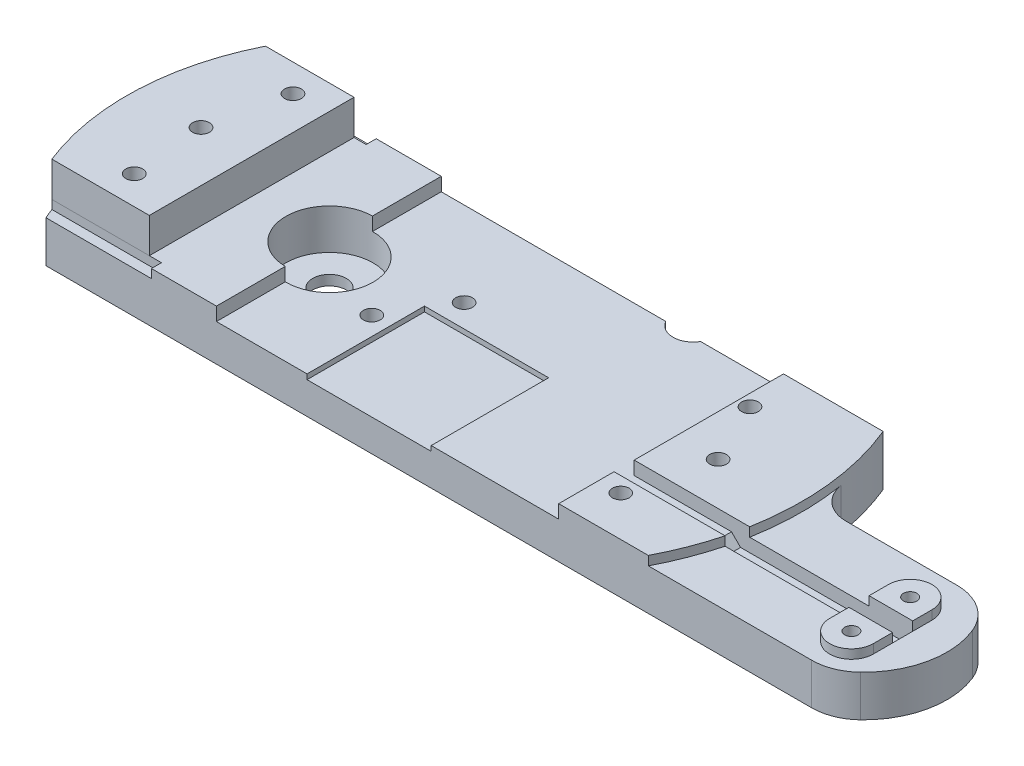
SolidWorks part; units mm, degrees
ref_plane "Front Plane" through (0, 0, 0) normal (0, 0, 1) x (1, 0, 0)
ref_plane "Top Plane" through (0, 0, 0) normal (0, 1, 0) x (1, 0, 0)
ref_plane "Right Plane" through (0, 0, 0) normal (1, 0, 0) x (0, 0, -1)
sketch "Sketch1" plane through (0, 0, 0) normal (0, 1, 0) x (1, 0, 0)
  line L1 (-97.5, -33.5) -> (97.5, -33.5)
  line L2 (-97.5, -33.5) -> (-97.5, 33.5)
  line L3 (-97.5, 33.5) -> (97.5, 33.5)
  line L4 (97.5, -33.5) -> (97.5, 33.5)
  line L5 (-97.5, -33.5) -> (97.5, 33.5) construction
  line L6 (-97.5, 33.5) -> (97.5, -33.5) construction
  point P0 (0, 0)
  dimension "D1" = 67
  dimension "D2" = 195
extrude "Boss-Extrude1" add sketch "Sketch1" along normal blind 25.4
sketch "Sketch2" plane through (0, 0, 0) normal (0, -1, 0) x (1, 0, 0)
  line L0 (-97.5, -33.5) -> (-97.5, 33.5) construction
  line L1 (97.5, 33.5) -> (97.5, -33.5) construction
  line L2 (97.5, 33.5) -> (88.5, 33.5)
  line L3 (-97.5, 33.5) -> (97.5, 33.5) construction
  line L4 (97.5, -33.5) -> (91.5, -33.5)
  line L5 (97.5, -33.5) -> (-97.5, -33.5) construction
  line L6 (-97.5, 33.5) -> (-91, 33.5)
  line L7 (-97.5, -33.5) -> (-88, -33.5)
  circle A0 centre (18.0922, -3.2198) radius 79.4078
  circle A1 centre (-22.6589, 2.9929) radius 74.8411
  line M7 (97.5, -33.5) -> (97.5, 33.5)
  line M8 (97.5, 33.5) -> (-97.5, 33.5)
  line M9 (-97.5, 33.5) -> (-97.5, -33.5)
  line M10 (-97.5, -33.5) -> (97.5, -33.5)
  dimension "D1" = 9
  dimension "D2" = 6
  dimension "D3" = 6.5
  dimension "D4" = 9.5
extrude "Cut-Extrude1" cut sketch "Sketch2" against normal through all contours A0 M7 M8 | A0 M10 M7 | A1 M9 M10 | A1 M8 M9 region at (94.8284, 0, 24.4273) region at (95.7123, 0, -25.9883) region at (-95.5654, 0, 25.941) region at (-94.6839, 0, -24.4966)
sketch "Sketch3" plane through (0, 0, 33.5) normal (0, 0, -1) x (-1, 0, 0)
  line L0 (97.5, 25.4) -> (63.2, 25.4)
  line L2 (63.2, 25.4) -> (63.2, 15)
  line L3 (63.2, 15) -> (40.2, 15)
  line L4 (40.2, 15) -> (40.2, 11)
  line L5 (40.2, 11) -> (-61.8, 11)
  line L6 (-91.5, 25.4) -> (88, 25.4) construction
  line L10 (97.5, 0) -> (97.5, 25.4) construction
  line L11 (-61.8, 11) -> (-61.8, 15)
  line L12 (-61.8, 15) -> (-97.5, 15)
  line L13 (-97.5, 25.4) -> (-97.5, 0) construction
  line L14 (-97.5, 15) -> (-97.5, 25.4)
  line L15 (-97.5, 25.4) -> (63.2, 25.4)
  line M13 (-88.5, 0) -> (-88.5, 25.4)
  line M14 (-88.5, 25.4) -> (91, 25.4)
  dimension "D1" = 10.4
  dimension "D2" = 34.3
  dimension "D3" = 23
  dimension "D4" = 4
  dimension "D5" = 102
extrude "Cut-Extrude2" cut sketch "Sketch3" along normal through all contours L11 L12 L2 L3 L4 L5 M13 M14 | L2 L3 L4 L5 L11 L12 L14 L15 region at (12.2699, 18.7206, 33.5)
sketch "Sketch4" plane through (0, 25.4, 0) normal (0, 1, 0) x (1, 0, 0)
  line L0 (-59.5873, 33.5) -> (-59.5873, 30.5)
  line L1 (-63.2, 33.5) -> (-88, 33.5) construction
  line L2 (-59.5873, 30.5) -> (-89.5873, 30.5)
  line L3 (-59.5873, -33.5) -> (-59.5873, -30.5)
  line L4 (-91, -33.5) -> (-63.2, -33.5) construction
  line L5 (-59.5873, -30.5) -> (-92.2617, -30.5)
  line L6 (-59.5873, 33.5) -> (-63.2, 33.5)
  line L7 (-59.5873, -33.5) -> (-63.2, -33.5)
  arc A0 (-88, 33.5) -> (-91, -33.5) centre (-22.6589, -2.9929) ccw construction
  line M5 (-91, -33.5) -> (-63.2, -33.5)
  line M6 (-63.2, -33.5) -> (-63.2, 33.5)
  line M7 (-63.2, 33.5) -> (-88, 33.5)
  arc M8 (-88, 33.5) -> (-91, -33.5) centre (-22.6589, -2.9929) ccw
  dimension "D1" = 3
  dimension "D2" = 3
  dimension "D3" = 30
extrude "Cut-Extrude3" cut sketch "Sketch4" against normal blind 13 contours L2 M6 M7 M8 | L0 L6 L2 M6 | L5 M6 M8 M5 | L7 L3 L5 M6 region at (-61.3937, 25.4, -32) region at (-76.0082, 25.4, -31.9845) region at (-77.4242, 25.4, 31.9889) region at (-61.3937, 25.4, 32)
sketch "Sketch6" plane through (0, 0, 0) normal (0, -1, 0) x (1, 0, 0)
  line L0 (-63.2, -33.5) -> (-97.5, -33.5)
  line L1 (91.5, -33.5) -> (-88, -33.5) construction
  line L2 (-63.2, -33.5) -> (-63.2, 33.5)
  line L3 (-91, 33.5) -> (88.5, 33.5) construction
  line L4 (-63.2, -9) -> (-28.1, -9) construction
  line L5 (-63.2, 8.7) -> (-18.7, 8.7) construction
  line L6 (-63.2, -8.3) -> (-8.2, -8.3) construction
  line L8 (91.5, -33.5) -> (-88, -33.5) construction
  line L9 (-97.5, -33.5) -> (-97.5, 33.5)
  line L10 (-97.5, 33.5) -> (-63.2, 33.5)
  circle A1 centre (-18.7, 8.7) radius 2.5
  circle A2 centre (74.1, -1.7) radius 2.5
  circle A3 centre (68.3, 21.5) radius 2.5
  circle A4 centre (65.3, -20) radius 2.5
  circle A5 centre (-8.2, -8.3) radius 2.5
  circle A6 centre (-76.2, 22) radius 2.5
  circle A7 centre (-78.2, 0.1) radius 2.5
  circle A8 centre (-73.2, -22.3) radius 2.5
  arc A10 (-91, 33.5) -> (-88, -33.5) centre (-22.6589, 2.9929) ccw construction
  dimension "D22" = 5
  dimension "D3" = 35.1
  dimension "D4" = 34.3
  dimension "D5" = 44.5
  dimension "D6" = 24.5
  dimension "D7" = 55
  dimension "D8" = 42.2
  dimension "D9" = 137.3
  dimension "D10" = 128.5
  dimension "D11" = 131.5
  dimension "D12" = 10
  dimension "D13" = 15
  dimension "D14" = 13
  dimension "D15" = 11.2
  dimension "D16" = 33.6
  dimension "D17" = 55.5
  dimension "D18" = 31.8
  dimension "D19" = 55
  dimension "D20" = 13.5
  dimension "D21" = 25.2
extrude "Cut-Extrude4" cut sketch "Sketch6" against normal through all contours A5 | A1 | A6 | A7 | A8 | A4 | A2 | A3 region at (-18.7, 0, 8.7) region at (74.1, 0, -1.7) region at (68.3, 0, 21.5) region at (65.3, 0, -20) region at (-8.2, 0, -8.3) region at (-76.2, 0, 22) region at (-78.2, 0, 0.1) region at (-73.2, 0, -22.3)
sketch "Sketch7" plane through (0, 11, 0) normal (0, 1, 0) x (1, 0, 0)
  line L1 (-13.2, 1.5) -> (23.8, 1.5)
  line L2 (-13.2, 1.5) -> (-13.2, -33.5)
  line L3 (-13.2, -33.5) -> (23.8, -33.5)
  line L4 (23.8, 1.5) -> (23.8, -33.5)
  line L8 (-63.2, 30.5) -> (-63.2, -30.5) construction
  line L9 (-63.2, 30.5) -> (-63.2, -30.5) construction
  line L10 (-40.2, -33.5) -> (61.8, -33.5) construction
  dimension "D1" = 50
  dimension "D2" = 87
  dimension "D3" = 35
extrude "Cut-Extrude5" cut sketch "Sketch7" against normal blind 1.5
sketch "Sketch8" plane through (0, 25.4, 0) normal (0, 1, 0) x (1, 0, 0)
  line L0 (-59.5873, -33.5) -> (-97.5, -33.5)
  line L1 (-97.5, -33.5) -> (-97.5, 33.5)
  line L3 (-97.5, 33.5) -> (31.9, 33.5)
  line L6 (31.9, 36.5) -> (31.9, 30.5)
  line L7 (31.9, 33.5) -> (37.0962, 33.5)
  line L10 (-59.5873, 33.5) -> (-88, 33.5) construction
  line L11 (-40.2, 33.5) -> (61.8, 33.5) construction
  circle A1 centre (31.9, 36.5) radius 6
  arc A2 (-89.5873, 30.5) -> (-92.2617, -30.5) centre (-22.6589, -2.9929) ccw construction
  dimension "D1" = 12
  dimension "D2" = 129.4
extrude "Cut-Extrude6" cut sketch "Sketch8" against normal blind 18.5 contours L6 A1 L7 | L3 A1 L6 region at (29.8648, 25.4, -32.2699) region at (33.9352, 25.4, -32.2699)
sketch "Sketch9" plane through (0, 0, 0) normal (0, -1, 0) x (1, 0, 0)
  line L0 (88.5, 33.5) -> (137.2004, 33.5)
  line L1 (139.5727, -7.5) -> (97.3846, -7.5)
  arc A0 (153.4738, 1.8643) -> (147.5429, 29.3643) centre (130.3054, 11.2571) ccw
  arc A1 (91.5, -33.5) -> (88.5, 33.5) centre (18.0922, -3.2198) ccw construction
  arc A2 (142.3827, -10.6321) -> (147.5429, 29.3643) centre (130.3054, 11.2571) ccw construction
  arc A3 (147.5429, 29.3643) -> (137.2004, 33.5) centre (137.2004, 18.5) ccw
  arc A4 (147.5429, 29.3643) -> (137.9704, 33.4802) centre (137.2004, 18.5) ccw construction
  arc A5 (139.5727, -7.5) -> (153.4738, 1.8643) centre (139.5727, 7.5) ccw
  circle A6 centre (112.8948, -27.5) radius 16 construction
  circle A7 centre (103.4238, 59.4942) radius 16 construction
  circle A8 centre (112.8948, -27.5) radius 20 construction
  arc A9 (97.3846, -7.5) -> (88.5, 33.5) centre (18.0922, -3.2198) ccw
  circle A10 centre (138.3, 5.25) radius 2
  circle A11 centre (138.3, 22.75) radius 2
  circle A12 centre (138.3, 22.75) radius 2 construction
  circle A13 centre (138.3, 5.25) radius 2 construction
  point P35 (112.8948, -27.5)
  dimension "D1" = 4
extrude "Boss-Extrude2" add sketch "Sketch9" against normal offset from surface (12.3 mm away) 1.3 up to face at (-16.2, 11, 8.7) offset beyond the face yes
fillet "Fillet1" radius 10 1 edges at (97.3846, 6.15, -7.5)
sketch "Sketch10" plane through (0, 0, 0) normal (0, -1, 0) x (1, 0, 0)
  circle A0 centre (-40.0178, 0) radius 13
  dimension "D1" = 26
extrude "Cut-Extrude7" cut sketch "Sketch10" against normal up to surface (15 mm away) from offset 3 up to face at (-55.6437, 15, 0) offset against normal yes
sketch "Sketch13" plane through (0, 0, 0) normal (0, -1, 0) x (1, 0, 0)
  circle A0 centre (-40.0178, 0) radius 5
  dimension "D1" = 10
extrude "Cut-Extrude9" cut sketch "Sketch13" against normal through all
sketch "Sketch11" plane through (0, 12.3, 0) normal (0, 1, 0) x (1, 0, 0)
  line L0 (138.3, -5.25) -> (138.3, -22.75) construction
  line L1 (144.8, -5.25) -> (144.8, -22.75)
  line L2 (131.8, -5.25) -> (131.8, -22.75)
  line L3 (131.8, -11) -> (144.8, -11)
  line L4 (131.8, -17) -> (144.8, -17)
  line L5 (131.8, -14) -> (144.8, -14) construction
  arc A0 (144.8, -5.25) -> (131.8, -5.25) centre (138.3, -5.25) ccw
  arc A1 (131.8, -22.75) -> (144.8, -22.75) centre (138.3, -22.75) ccw
  point P4 (138.3, -14)
  circle M15 centre (138.3, -22.75) radius 2
  circle M16 centre (138.3, -5.25) radius 2
  dimension "D1" = 13
  dimension "D2" = 6
extrude "Boss-Extrude3" add sketch "Sketch11" along normal up to surface (2.7 mm away) contours L1 A0 L2 L3 M16 | L2 A1 L1 L4 M15 region at (144.6214, 12.3, 8.125) region at (144.6214, 12.3, 19.875) up to face at (70.8, 15, 21.5)
split "Split1" bodies to split 113 resulting bodies 114 115 split by face at (-53.8367, 15, 0)
sketch "Sketch12" plane through (0, 0, 11) normal (0, 0, 1) x (1, 0, 0)
  line L0 (144.8, 15) -> (144.8, 8.3)
  line L1 (144.8, 8.3) -> (93.5, 8.3)
  line L3 (97.5, 12.3) -> (88.5, 12.3) construction
  line L4 (90.8, 11) -> (61.8, 11)
  line L5 (61.8, 11) -> (61.8, 15)
  line L6 (61.8, 15) -> (88.5, 15) construction
  line L7 (61.8, 15) -> (144.8, 15)
  line L10 (97.5, 12.3) -> (93.5, 12.3) construction
  line L12 (88.5, 12.3) -> (137.2004, 12.3) construction
  line L13 (93.5, 12.3) -> (93.5, 8.3) construction
  line L14 (61.8, 11) -> (61.8, 15) construction
  line L15 (23.8, 11) -> (61.8, 11) construction
  line L16 (93.5, 8.3) -> (90.8, 11)
  dimension "D1" = 45
extrude "Cut-Extrude8" cut sketch "Sketch12" along normal up to surface (6 mm away) up to face at (138.3, 13.65, 17)
